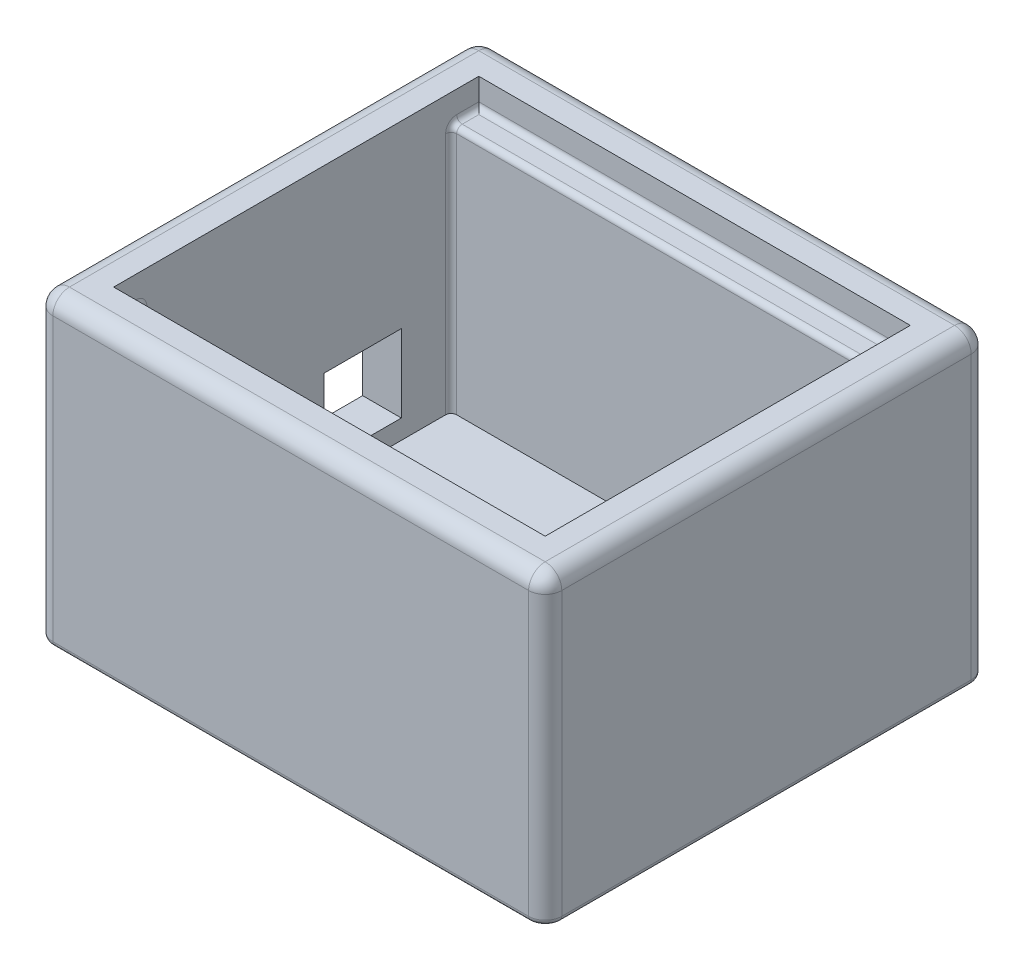
SolidWorks part; units mm, degrees
ref_plane "Frontal Plane" through (0, 0, 0) normal (0, 0, 1) x (1, 0, 0)
ref_plane "Horizontal Plane" through (0, 0, 0) normal (0, 1, 0) x (1, 0, 0)
ref_plane "Profile Plane" through (0, 0, 0) normal (1, 0, 0) x (0, 0, -1)
sketch "Sketch1" plane through (0, 0, 0) normal (0, 1, 0) x (1, 0, 0)
  line L1 (0, 0) -> (92, 0)
  line L2 (0, 0) -> (0, -80)
  line L3 (0, -80) -> (92, -80)
  line L4 (92, 0) -> (92, -80)
  dimension "D1" = 92
  dimension "D2" = 80
extrude "Boss-Extrude1" add sketch "Sketch1" along normal blind 55
sketch "Sketch2" plane through (0, 55, 0) normal (0, 1, 0) x (1, 0, 0)
  line L0 (92, 0) -> (0, 0) construction
  line L1 (7, -12) -> (85, -12)
  line L2 (7, -12) -> (7, -68)
  line L3 (7, -68) -> (85, -68)
  line L4 (85, -12) -> (85, -68)
  line L5 (0, -80) -> (92, -80) construction
  line L6 (92, -80) -> (92, 0) construction
  line L7 (0, 0) -> (0, -80) construction
  dimension "D1" = 12
  dimension "D2" = 12
  dimension "D3" = 7
  dimension "D4" = 7
extrude "Cut-Extrude1" cut sketch "Sketch2" against normal blind 50
sketch "Sketch3" plane through (0, 55, 0) normal (0, 1, 0) x (1, 0, 0)
  line L0 (7, -12) -> (7, -7)
  line L1 (7, -7) -> (85, -7)
  line L2 (85, -7) -> (85, -12)
  line L3 (85, -12) -> (7, -12)
  line L4 (7, -68) -> (7, -73)
  line L5 (7, -73) -> (85, -73)
  line L6 (85, -73) -> (85, -68)
  line L7 (85, -68) -> (7, -68)
  dimension "D1" = 5
  dimension "D2" = 5
extrude "Cut-Extrude2" cut sketch "Sketch3" against normal blind 5
fillet "Fillet_top" radius 3 4 edges at (46, 55, 0) (92, 55, 40) (46, 55, 80) (0, 55, 40)
fillet "Fillet_edges" radius 3 8 edges at (0.8787, 54.1213, 0.8787) (91.1213, 54.1213, 0.8787) (91.1213, 54.1213, 79.1213) (0.8787, 54.1213, 79.1213) (0, 26, 0) (92, 26, 0) (92, 26, 80) (0, 26, 80)
fillet "Fillet_bottom" radius 1 8 edges at (0.8787, 0, 79.1213) (0, 0, 40) (0.8787, 0, 0.8787) (46, 0, 0) (91.1213, 0, 0.8787) (92, 0, 40) (91.1213, 0, 79.1213) (46, 0, 80)
fillet "Fillet4" radius 1 12 edges at (85, 27.5, 68) (7, 27.5, 68) (7, 27.5, 12) (85, 27.5, 12) (85, 50, 70.5) (46, 50, 73) (7, 50, 70.5) (46, 50, 68) (7, 50, 9.5) (46, 50, 7) (85, 50, 9.5) (46, 50, 12)
sketch "Sketch5" plane through (0, 0, 0) normal (-1, 0, 0) x (0, 0, 1)
  line L0 (0, 1) -> (0, 52) construction
  line L1 (21, 8.5) -> (35, 8.5)
  line L2 (21, 8.5) -> (21, 22.5)
  line L3 (21, 22.5) -> (35, 22.5)
  line L4 (35, 8.5) -> (35, 22.5)
  line L8 (77, 0) -> (3, 0) construction
  dimension "D1" = 21
  dimension "D3" = 8.5
  dimension "D4" = 14
  dimension "D5" = 14
extrude "Cut-Extrude4" cut sketch "Sketch5" against normal up to next
